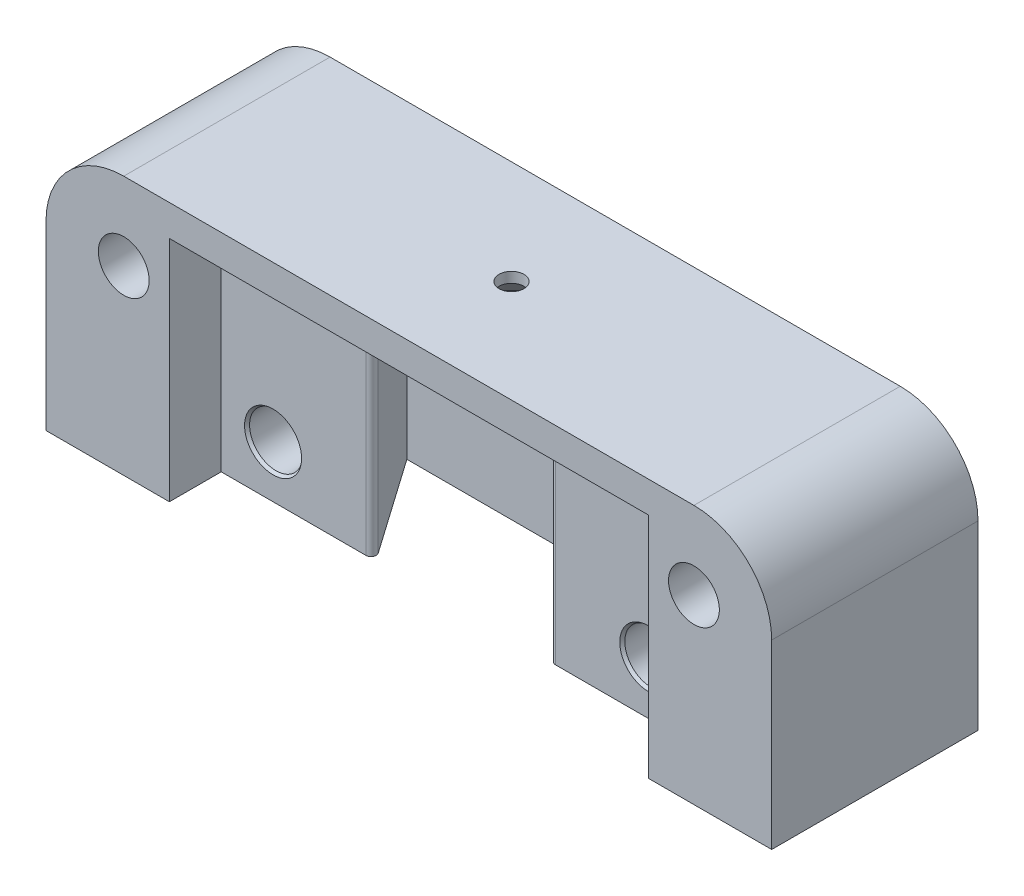
SolidWorks part; units mm, degrees
ref_plane "Front Plane" through (0, 0, 0) normal (0, 0, 1) x (1, 0, 0)
ref_plane "Top Plane" through (0, 0, 0) normal (0, 1, 0) x (1, 0, 0)
ref_plane "Right Plane" through (0, 0, 0) normal (1, 0, 0) x (0, 0, -1)
sketch "Sketch1" plane through (0, 0, 0) normal (0, 1, 0) x (1, 0, 0)
  line L0 (-1035, 0) -> (48965, 0) construction
  line L1 (-35, -10) -> (-23.0979, -10) construction
  line L2 (-35, -10) -> (-35, 10)
  line L3 (-35, 10) -> (35, 10)
  line L4 (35, -10) -> (35, 10)
  line L5 (0, -990) -> (0, 49010) construction
  line L6 (27.5, -30.8284) -> (27.5, 30.8284) construction
  line L7 (-27.5, -30.1183) -> (-27.5, 30.1183) construction
  line L8 (-15, 5) -> (15, 5) construction
  line L9 (15, 5) -> (7.9979, -5) construction
  line L10 (7.9979, -5) -> (22.9979, -5) construction
  line L11 (-7.9979, -5) -> (-22.9979, -5) construction
  line L12 (-15, 5) -> (-7.9979, -5) construction
  line L13 (22.9979, -5) -> (22.9979, -10) construction
  line L14 (-22.9979, -10) -> (-22.9979, -5) construction
  line L15 (22.9979, -10) -> (35, -10) construction
  line L16 (-8.19, -4.9) -> (-22.9979, -4.9)
  line L17 (-15.1921, 5.1) -> (-8.19, -4.9)
  line L18 (-15.1921, 5.1) -> (15.1921, 5.1)
  line L19 (15.1921, 5.1) -> (8.19, -4.9)
  line L20 (8.19, -4.9) -> (22.9979, -4.9)
  line L21 (23.0979, -9.9) -> (35, -9.9)
  line L22 (-35, -9.9) -> (-23.0979, -9.9)
  line L23 (23.0979, -5) -> (23.0979, -9.9)
  line L24 (-23.0979, -9.9) -> (-23.0979, -5)
  line L25 (-23.0979, -5) -> (-23.0979, -4.9)
  line L26 (-23.0979, -4.9) -> (-22.9979, -4.9)
  line L27 (22.9979, -4.9) -> (23.0979, -4.9)
  line L28 (23.0979, -4.9) -> (23.0979, -5)
  line L29 (23.0979, -5) -> (23.0979, -10) construction
  line L30 (22.9979, -9.9) -> (35, -9.9) construction
  line L31 (-35, -9.9) -> (-22.9979, -9.9) construction
  line L32 (-35, -10) -> (-22.9979, -10) construction
  line L33 (-23.0979, -10) -> (-23.0979, -5) construction
  point P7 (-35, 0)
  point P10 (0, 10)
  point P13 (27.5, 0)
  point P16 (-27.5, 0)
  point P22 (0, 5)
  dimension "D1" = 20
  dimension "D2" = 70
  dimension "D3" = 55
  dimension "D4" = 27.5
  dimension "D5" = 55
  dimension "D6" = 5
  dimension "D7" = 5
  dimension "D8" = 15
  dimension "D9" = 15
  dimension "D10" = 15
  dimension "D11" = 0.1
  dimension "D12" = 0.1
extrude "Boss-Extrude1" add sketch "Sketch1" along normal blind 25 contours L27 L28 L23 L21 L4 L3 L2 L22 L24 L25 L26 L16 L17 L18 L19 L20 region at (-34.2723, 0, -0.05)
sketch "Sketch2" plane through (0, 0, -10) normal (0, 0, -1) x (-1, 0, 0)
  line L0 (0, -977.5) -> (0, 49022.5) construction
  line L1 (35, 25) -> (-35, 25) construction
  circle A0 centre (-27.5, 17.5) radius 2.45
  circle A1 centre (27.5, 17.5) radius 2.45
  point P5 (0, 25)
  dimension "D1" = 55
  dimension "D2" = 27.5
  dimension "D3" = 7.5
  dimension "D4" = 7.5
extrude "Cut-Extrude1" cut sketch "Sketch2" against normal blind 25
fillet "Fillet1" radius 7.5 2 edges at (-35, 25, -0.05) (35, 25, -0.05)
sketch "Sketch3" plane through (0, 25, 0) normal (0, 1, 0) x (1, 0, 0)
  line L1 (-27.5, -9.9) -> (27.5, -9.9)
  line L2 (-27.5, -9.9) -> (-27.5, 10)
  line L3 (-27.5, 10) -> (27.5, 10)
  line L4 (27.5, -9.9) -> (27.5, 10)
extrude "Boss-Extrude2" add sketch "Sketch3" against normal blind 3
hole_wizard "CSK for M2 Flat Head Machine Screw1" positions "Sketch4" profile "Sketch5" countersink size "M2" standard "ANSI Metric"
sketch "Sketch4" plane through (0, 22, 0) normal (0, -1, 0) x (-1, 0, 0)
  point P0 (0, 0)
sketch "Sketch5" plane through (0, 22, 0) normal (1, 0, 0) x (0, 0, -1)
  line L0 (0, 0) -> (0, 10.721)
  line L1 (0, 10.721) -> (1.2, 10)
  line L2 (1.2, 10) -> (1.2, 2)
  line L3 (1.2, 2) -> (3.2, 0)
  line L5 (3.2, 0) -> (0, 0)
  line L6 (-1.2, 2) -> (-3.2, 0) construction
  line L10 (0, 10.721) -> (-1.2, 10) construction
  line L11 (0, -6.35) -> (0, 107.95) construction
  dimension "Hole Dia." = 2.4
  dimension "Hole Depth" = 10
  dimension "Near C'Sink Dia." = 6.4
  dimension "Near C'Sink Angle" = 90
  dimension "Drill Angle" = 118
fillet "Fillet2" radius 0.5 2 edges at (8.19, 11, 4.9) (-8.19, 11, 4.9)
ref_plane "Plane1" through (0, 17.5, 0) normal (0, 1, 0) x (1, 0, 0)
sketch "Sketch10" plane through (0, 17.5, 0) normal (0, 1, 0) x (1, 0, 0)
  line L0 (27.5, -990.029) -> (27.5, 49009.971) construction
  line L1 (-27.5, -990.1822) -> (-27.5, 49009.8178) construction
  line L2 (-29.95, 10) -> (-29.95, -9.9) construction
  line L3 (-27.5, 10.0056) -> (-33.6, 10.0056)
  line L4 (-27.5, 10.0056) -> (-27.5, 6.0525)
  line L5 (-29.95, 6.0525) -> (-31.4538, 6.0525)
  line L6 (-33.6, 10.0056) -> (-33.6, 5.6056)
  line L7 (-31.4538, 6.0525) -> (-29.95, 6.0525)
  line L8 (-32.25, 5.2132) -> (-32.25, 0.0525)
  line L9 (-32.25, 0.0525) -> (-27.5, 0.0525)
  line L10 (-27.5, 6.0525) -> (-27.5, 0.0525)
  line L11 (-29.95, 0.05) -> (-31.4538, 0.05)
  line L12 (-29.95, 0.05) -> (-29.95, 6.0525)
  line L13 (-29.95, 6.0525) -> (-31.4538, 6.0525)
  line L14 (-31.4538, 0.05) -> (-31.4538, 6.0525)
  line L16 (-33.6, 5.6056) -> (-32.25, 5.2132)
  line L17 (-30.7019, 6.0525) -> (-31.4538, 6.784)
  line L18 (-29.95, 6.0525) -> (-31.4538, 6.0525)
  line L19 (-29.95, 6.0525) -> (-29.95, 9.9933)
  line L20 (-29.95, 9.9933) -> (-31.4538, 9.9933)
  line L21 (-31.4538, 6.784) -> (-31.4538, 9.9933)
  line L22 (0, -1000) -> (0, 49000) construction
  line L23 (31.4538, 6.784) -> (31.4538, 9.9933)
  line L24 (29.95, 9.9933) -> (31.4538, 9.9933)
  line L25 (29.95, 6.0525) -> (29.95, 9.9933)
  line L26 (29.95, 6.0525) -> (31.4538, 6.0525)
  line L27 (30.7019, 6.0525) -> (31.4538, 6.784)
  line L28 (33.6, 5.6056) -> (32.25, 5.2132)
  line L29 (31.4538, 0.05) -> (31.4538, 6.0525)
  line L30 (29.95, 6.0525) -> (31.4538, 6.0525)
  line L31 (29.95, 0.05) -> (29.95, 6.0525)
  line L32 (29.95, 0.05) -> (31.4538, 0.05)
  line L33 (27.5, 6.0525) -> (27.5, 0.0525)
  line L34 (32.25, 0.0525) -> (27.5, 0.0525)
  line L35 (32.25, 5.2132) -> (32.25, 0.0525)
  line L36 (31.4538, 6.0525) -> (29.95, 6.0525)
  line L37 (33.6, 10.0056) -> (33.6, 5.6056)
  line L38 (29.95, 6.0525) -> (31.4538, 6.0525)
  line L39 (27.5, 10.0056) -> (27.5, 6.0525)
  line L40 (27.5, 10.0056) -> (33.6, 10.0056)
  dimension "D1" = 2.45
  dimension "D2" = 2.45
  dimension "D3" = 6.1
  dimension "D4" = 4.4
  dimension "D5" = 4.75
revolve "Cut-Revolve1" cut sketch "Sketch10" angle 360 about L1 region at (-27.6167, 17.5, -8.029)
revolve "Cut-Revolve2" cut sketch "Sketch10<3>" angle 360 about L0 region at (31.5705, 17.5, -8.3887)
sketch "Sketch10<3>" plane through (0, 17.5, 0) normal (0, 1, 0) x (1, 0, 0) same geometry as "Sketch10"
hole_wizard "CSK for M5 Flat Head Machine Screw1" positions "Sketch13" profile "Sketch12" countersink size "M5" standard "ANSI Metric"
sketch "Sketch13" plane through (0, 0, 4.9) normal (0, 0, 1) x (1, 0, 0)
  line L0 (-23.0979, 22) -> (-23.0979, 0) construction
  line L1 (-23.0979, 0) -> (-9.1505, 0) construction
  line L2 (9.1505, 0) -> (23.0979, 0) construction
  line L3 (23.0979, 22) -> (23.0979, 0) construction
  point P0 (-18.0979, 5)
  point P2 (18.0979, 5)
  dimension "D1" = 5
  dimension "D2" = 5
  dimension "D3" = 5
  dimension "D4" = 5
sketch "Sketch12" plane through (-18.0979, 5, 4.9) normal (1, 0, 0) x (0, -1, 0)
  line L0 (0, 0) -> (0, 6)
  line L1 (0, 6) -> (2.55, 6)
  line L2 (2.55, 6) -> (2.55, 0.2856)
  line L3 (2.55, 0.2856) -> (2.75, 0)
  line L5 (2.75, 0) -> (0, 0)
  line L6 (-2.55, 0.2856) -> (-2.75, 0) construction
  line L10 (0, 6) -> (-2.55, 6) construction
  line L11 (0, -6.35) -> (0, 107.95) construction
  dimension "Hole Dia." = 5.1
  dimension "Hole Depth" = 6
  dimension "Near C'Sink Dia." = 5.5
  dimension "Near C'Sink Angle" = 70
  dimension "Drill Angle" = 180
